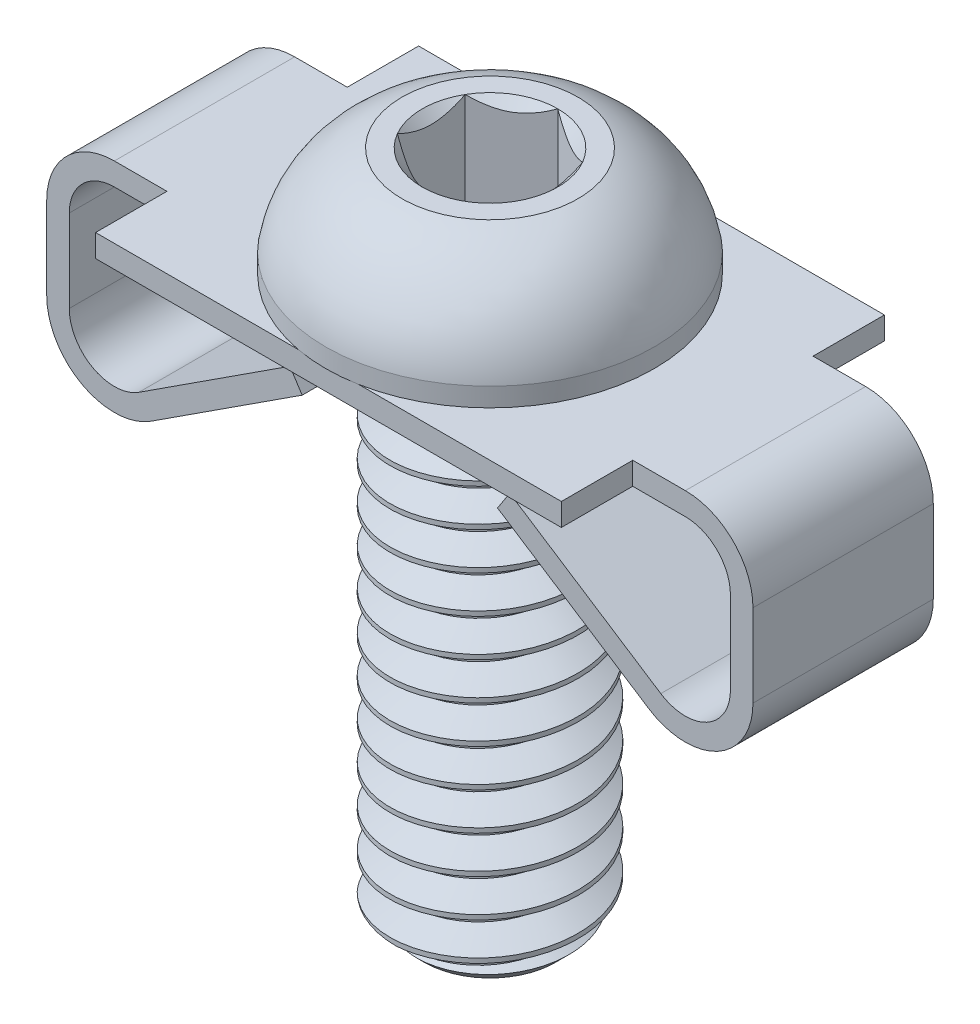
SolidWorks part; units mm, degrees
material "Alloy Steel"
ref_plane "Front Plane" through (0, 0, 0) normal (0, 0, 1) x (1, 0, 0)
ref_plane "Top Plane" through (0, 0, 0) normal (0, 1, 0) x (1, 0, 0)
ref_plane "Right Plane" through (0, 0, 0) normal (1, 0, 0) x (0, 0, -1)
sketch "Sketch1" plane through (0, 0, 0) normal (0, 0, 1) x (1, 0, 0)
  line L0 (-11.938, 0) -> (11.938, 0)
  line L1 (0, 0) -> (0, -19.05)
  line L2 (-11.938, -7.366) -> (11.938, -7.366)
  line L3 (-7.874, 0) -> (-7.874, -7.366) construction
  line L4 (-7.874, 0) -> (7.874, 0) construction
  line L5 (7.874, 0) -> (7.874, -7.366) construction
  dimension "D1" = 23.876
  dimension "D2" = 19.05
  dimension "D3" = 7.366
  dimension "D4" = 15.748
sketch "Sketch2" plane through (0, 0, 0) normal (0, 1, 0) x (1, 0, 0)
  circle A0 centre (0, 0) radius 3.175
  dimension "D1" = 6.35
curve "Helix/Spiral1" pitch 1.27 height 22.225 turns 17.5
sketch "Sketch3" plane through (0, 0, 0) normal (0, 1, 0) x (1, 0, 0)
  circle A1 centre (0, 0) radius 3.175
  circle A2 centre (0, 0) radius 3.175
  dimension "D1" = 0
extrude "Extrude1" add sketch "Sketch3" against normal up to vertex (19.05 mm away) up to point (0, -19.05, 0)
chamfer "Chamfer1" distance 0.9525 angle 45 1 edges at (0, -19.05, 3.175)
sketch "Sketch4" plane through (0, 0, 0) normal (0, 0, 1) x (1, 0, 0)
  line L0 (3.175, 0) -> (3.175, -1.1113)
  line L1 (3.175, 0) -> (2.3501, -0.4763)
  line L2 (2.3501, -0.4763) -> (2.3501, -0.635)
  line L3 (2.3501, -0.635) -> (3.175, -1.1113)
  line L4 (2.3501, -0.5556) -> (3.175, -0.5556) construction
  line L5 (2.7626, -0.2381) -> (2.7626, -0.8731) construction
  dimension "D1" = 0.1588
  dimension "D2" = 0.635
  dimension "D3" = 60
sweep "Cut-Sweep1" cut profiles "Sketch4" path "Helix/Spiral1"
sketch "Sketch5" plane through (0, 0, 0) normal (0, 0, 1) x (1, 0, 0)
  line L0 (-11.938, -2.286) -> (-11.938, -5.08)
  line L1 (-8.4072, -6.9974) -> (-3.302, -3.683)
  line L2 (-9.652, 0) -> (0, 0)
  line L3 (-11.938, -7.366) -> (11.938, -7.366) construction
  line L4 (0, 0) -> (0, -0.762)
  line L6 (-8.8221, -6.3582) -> (-3.7169, -3.0439)
  line L7 (-11.176, -2.286) -> (-11.176, -5.08)
  line L8 (-9.652, -0.762) -> (0, -0.762)
  line L9 (-9.652, -0.762) -> (-0.762, -0.762) construction
  line L10 (-0.762, -0.762) -> (-0.762, -0.9525) construction
  line L11 (-3.7169, -3.0439) -> (-3.302, -3.683)
  line L12 (0, 0) -> (0, -0.9525) construction
  line L14 (-3.175, 0) -> (-3.175, -7.366) construction
  line L15 (3.175, 0) -> (-3.175, 0) construction
  line L16 (-3.302, 0) -> (-3.302, -7.366) construction
  arc A0 (-11.938, -2.286) -> (-9.652, 0) centre (-9.652, -2.286) cw
  arc A1 (-11.938, -5.08) -> (-8.4072, -6.9974) centre (-9.652, -5.08) ccw
  arc A2 (-11.176, -5.08) -> (-8.8221, -6.3582) centre (-9.652, -5.08) ccw
  arc A3 (-11.176, -2.286) -> (-9.652, -0.762) centre (-9.652, -2.286) cw
  point P9 (-11.938, 0)
  dimension "D1" = 2.286
  dimension "D3" = 3.683
  dimension "D2" = 0.762
  dimension "D4" = 0.127
extrude "Extrude2" add sketch "Sketch5" along normal mid plane 10.922 separate body
sketch "Sketch6" plane through (0, 0, 5.461) normal (0, 0, 1) x (1, 0, 0)
  line L0 (-11.938, -7.366) -> (11.938, -7.366) construction
  line L1 (-11.938, 0) -> (-7.874, 0)
  line L2 (-11.938, 0) -> (-11.938, -7.366)
  line L3 (-11.938, -7.366) -> (-8.975, -7.366)
  line L5 (-7.874, 0) -> (-7.874, -0.762)
  line L6 (-7.874, -0.762) -> (-3.302, -0.762)
  line L7 (-11.938, 0) -> (11.938, 0) construction
  line L8 (-7.874, 0) -> (-7.874, -7.366) construction
  line L9 (-9.652, -0.762) -> (0, -0.762) construction
  line L10 (-11.938, -2.286) -> (-11.938, -5.08) construction
  line L11 (-3.302, -3.683) -> (-3.302, -0.762)
  line L12 (-8.4072, -6.9974) -> (-3.302, -3.683) construction
  line L13 (-8.975, -7.366) -> (-3.302, -3.683)
extrude "Cut-Extrude2" cut sketch "Sketch6" against normal offset from surface (2.413 mm away) 3.048 up to plane "Front Plane"
mirror "Mirror4" about plane through (0, 0, 0) normal (0, 0, 1) of "Cut-Extrude2"
mirror "Mirror5" about plane through (0, 0, 0) normal (1, 0, 0) of bodies 107
sketch "Sketch7" plane through (0, 0, 0) normal (0, 1, 0) x (1, 0, 0)
  line L1 (0, 2.2914) -> (-1.9844, 1.1457)
  line L2 (-1.9844, 1.1457) -> (-1.9844, -1.1457)
  line L3 (-1.9844, -1.1457) -> (0, -2.2914)
  line L4 (0, -2.2914) -> (1.9844, -1.1457)
  line L5 (1.9844, -1.1457) -> (1.9844, 1.1457)
  line L6 (1.9844, 1.1457) -> (0, 2.2914)
  circle A0 centre (0, 0) radius 1.9844 construction
  circle A1 centre (0, 0) radius 5.5562
  dimension "D2" = 11.1125
  dimension "D1" = 3.9688
extrude "Extrude4" add sketch "Sketch7" along normal blind 3.683
sketch "Sketch8" plane through (0, 3.683, 0) normal (0, 1, 0) x (1, 0, 0)
  circle A0 centre (0, 0) radius 2.9766
  dimension "D1" = 5.9531
sketch "Sketch9" plane through (0, 0, 0) normal (0, 0, 1) x (1, 0, 0)
  line L0 (2.9766, 3.683) -> (-2.9766, 3.683) construction
  line L1 (-11.938, 0) -> (11.938, 0) construction
  line L3 (-5.5562, 0.635) -> (-5.5562, 3.683)
  line L4 (-2.9766, 3.683) -> (-5.5562, 3.683)
  line L5 (5.5562, 3.683) -> (-5.5562, 3.683) construction
  line L6 (-5.5562, 3.683) -> (-5.5562, 0) construction
  arc A0 (-2.9766, 3.683) -> (-5.5562, 0.635) centre (-1.7155, 0) ccw
  dimension "D1" = 0.635
revolve "Cut-Revolve1" cut sketch "Sketch9" angle 360 about L1
sketch "Sketch10" plane through (0, 3.683, 0) normal (0, 1, 0) x (1, 0, 0)
  circle A0 centre (0, 0) radius 2.2914
extrude "Cut-Extrude3" cut sketch "Sketch10" against normal through all draft 45
equation "\"D3@Helix/Spiral1\" = \"D2@Sketch1\"+.125"
equation "\"D1@Chamfer1\" = \"D4@Helix/Spiral1\"*.750"
equation "\"D1@Sketch4\" = \"D4@Helix/Spiral1\"*.125"
equation "\"D2@Sketch4\" = \"D4@Helix/Spiral1\"*.50"
equation "\"D3@Sketch5\" = \"D3@Sketch1\"*.5"
equation "\"D2@Sketch7\" = \"D1@Sketch7\"*2.8"
equation "\"D1@Extrude4\" = \"D3@Sketch1\"*.50"
equation "\"D1@Sketch8\" = \"D1@Sketch7\"*1.5"
